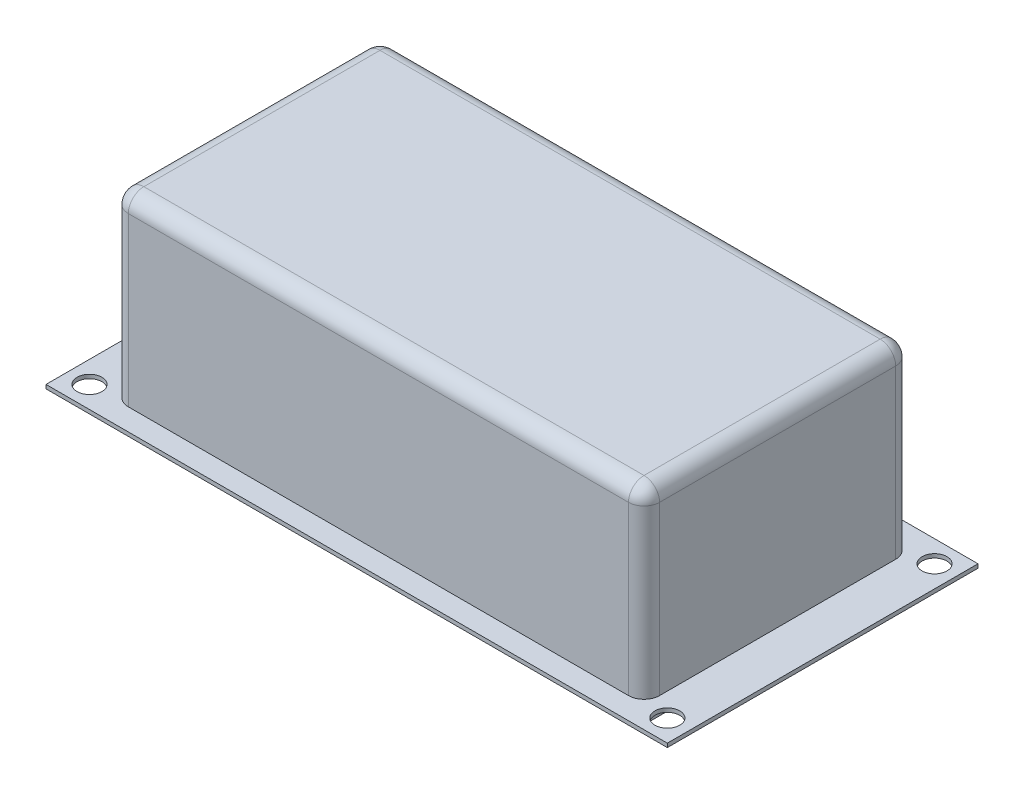
SolidWorks part; units mm, degrees
ref_plane "Front Plane" through (0, 0, 0) normal (0, 0, 1) x (1, 0, 0)
ref_plane "Top Plane" through (0, 0, 0) normal (0, 1, 0) x (1, 0, 0)
ref_plane "Right Plane" through (0, 0, 0) normal (1, 0, 0) x (0, 0, -1)
sketch "Sketch1" plane through (0, 0, 0) normal (0, 1, 0) x (1, 0, 0)
  line L1 (-50.8, 25.4) -> (50.8, 25.4)
  line L2 (-50.8, 25.4) -> (-50.8, -25.4)
  line L3 (-50.8, -25.4) -> (50.8, -25.4)
  line L4 (50.8, 25.4) -> (50.8, -25.4)
  line L5 (-50.8, 25.4) -> (50.8, -25.4) construction
  line L6 (-50.8, -25.4) -> (50.8, 25.4) construction
  point P0 (0, 0)
  dimension "D1" = 101.6
  dimension "D2" = 50.8
extrude "Boss-Extrude1" add sketch "Sketch1" along normal mid plane 0.635
sketch "Sketch2" plane through (0, 0.3175, 0) normal (0, 1, 0) x (1, 0, 0)
  circle A0 centre (-47.244, -21.844) radius 2.032
  dimension "D1" = 4.064
  dimension "D2" = 21.844
  dimension "D3" = 47.244
extrude "Cut-Extrude1" cut sketch "Sketch2" against normal through all
mirror "Mirror1" about plane through (0, 0, 0) normal (0, 0, 1) of "Cut-Extrude1"
mirror "Mirror2" about plane through (0, 0, 0) normal (1, 0, 0) of "Mirror1"
sketch "Sketch3" plane through (0, 0, 0) normal (0, 1, 0) x (1, 0, 0)
  line L1 (-43.434, 21.844) -> (43.434, 21.844)
  line L2 (-43.434, 21.844) -> (-43.434, -21.844)
  line L3 (-43.434, -21.844) -> (43.434, -21.844)
  line L4 (43.434, 21.844) -> (43.434, -21.844)
  line L5 (-43.434, 21.844) -> (43.434, -21.844) construction
  line L6 (-43.434, -21.844) -> (43.434, 21.844) construction
  circle A0 centre (-47.244, 21.844) radius 2.032 construction
  circle A1 centre (47.244, 21.844) radius 2.032 construction
  point P0 (0, 0)
  dimension "D1" = 3.81
  dimension "D2" = 0
extrude "Boss-Extrude2" add sketch "Sketch3" against normal blind 2.54
extrude "Boss-Extrude3" add sketch "Sketch3<2>" along normal blind 30.226
sketch "Sketch3<2>" plane through (0, 0, 0) normal (0, 1, 0) x (1, 0, 0) same geometry as "Sketch3"
fillet "Fillet1" radius 2.54 8 edges at (-43.434, 15.2717, -21.844) (0, 30.226, -21.844) (43.434, 15.2717, -21.844) (43.434, 30.226, 0) (43.434, 15.2717, 21.844) (0, 30.226, 21.844) (-43.434, 15.2717, 21.844) (-43.434, 30.226, 0)
